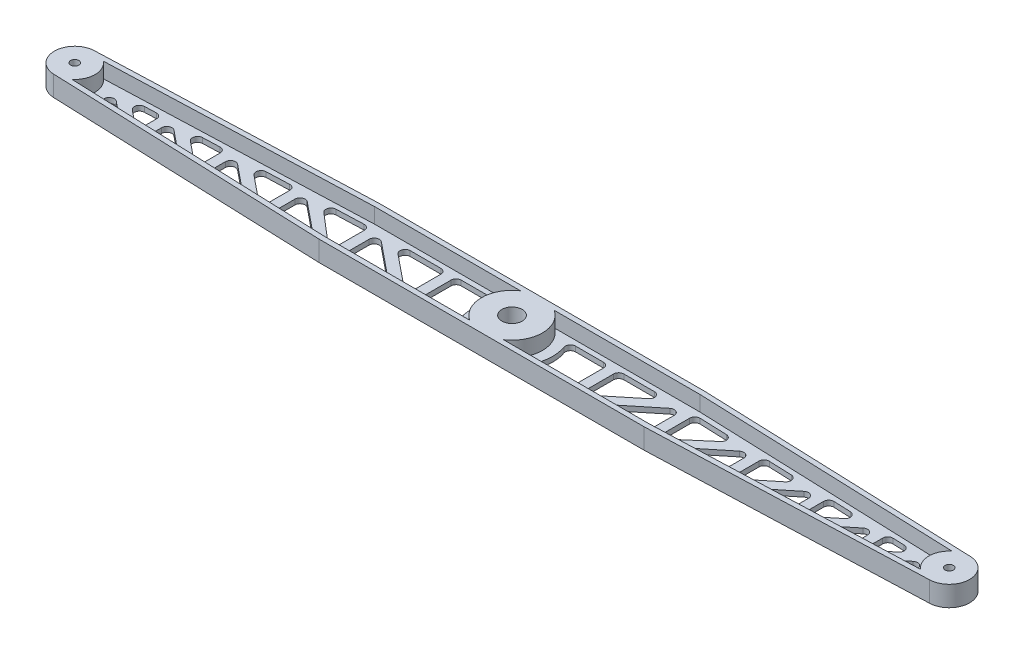
SolidWorks part; units mm, degrees
material "6061 Alloy"
ref_plane "Front Plane" through (0, 0, 0) normal (0, 0, 1) x (1, 0, 0)
ref_plane "Top Plane" through (0, 0, 0) normal (0, 1, 0) x (1, 0, 0)
ref_plane "Right Plane" through (0, 0, 0) normal (1, 0, 0) x (0, 0, -1)
sketch "Sketch1" plane through (0, 0, 0) normal (1, 0, 0) x (0, 0, -1)
  line L1 (-19.05, -6.35) -> (19.05, -6.35)
  line L2 (-19.05, -6.35) -> (-19.05, 6.35)
  line L3 (-19.05, 6.35) -> (19.05, 6.35)
  line L4 (19.05, -6.35) -> (19.05, 6.35)
  line L5 (-19.05, -6.35) -> (19.05, 6.35) construction
  line L6 (-19.05, 6.35) -> (19.05, -6.35) construction
  point P0 (0, 0)
  dimension "D1" = 38.1
  dimension "D2" = 12.7
extrude "Boss-Extrude1" add sketch "Sketch1" along normal mid plane 584.2
sketch "Sketch2" plane through (0, 6.35, 0) normal (0, 1, 0) x (1, 0, 0)
  circle A0 centre (0, 0) radius 6.35
  dimension "D1" = 12.7
extrude "Pivot Hole" cut sketch "Sketch2" against normal through all
hole_wizard "End Holes" positions "Sketch4" profile "Sketch3" tap size "1/4-20" standard "ANSI Inch" end condition through all
sketch "Sketch4" plane through (0, -6.35, 0) normal (0, -1, 0) x (-1, 0, 0)
  line L0 (273.05, 0) -> (292.1, 0) construction
  line L1 (292.1, -19.05) -> (292.1, 19.05) construction
  line L4 (-273.05, 0) -> (-292.1, 0) construction
  line L5 (-292.1, -19.05) -> (-292.1, 19.05) construction
  point P0 (273.05, 0)
  point P2 (-273.05, 0)
  dimension "D1" = 19.05
sketch "Sketch3" plane through (-273.05, -6.35, 0) normal (1, 0, 0) x (0, 0, -1)
  line L0 (0, 0) -> (0, 12.7)
  line L1 (0, 12.7) -> (2.5527, 12.7)
  line L2 (2.5527, 12.7) -> (2.5527, 0)
  line L5 (2.5527, 0) -> (0, 0)
  line L11 (0, -6.35) -> (0, 107.95) construction
  dimension "Thread Major Dia." = 5.1054
  dimension "Thru Tap Drill Depth" = 12.7
sketch "Sketch7" plane through (0, 6.35, 0) normal (0, 1, 0) x (1, 0, 0)
  line L0 (101.6, 19.05) -> (-101.6, 19.05)
  line L1 (292.1, 19.05) -> (-292.1, 19.05) construction
  line L2 (-101.6, 19.05) -> (-273.5194, 12.6913)
  line L3 (-273.5194, -12.6913) -> (-101.6, -19.05)
  line L4 (292.1, -19.05) -> (-292.1, -19.05) construction
  line L5 (-101.6, -19.05) -> (101.6, -19.05)
  line L6 (0, 19.05) -> (0, -19.05) construction
  line L7 (273.5194, -12.6913) -> (101.6, -19.05)
  line L8 (101.6, 19.05) -> (273.5194, 12.6913)
  line L13 (-292.1, 19.05) -> (-292.1, -19.05)
  line L14 (-292.1, -19.05) -> (292.1, -19.05)
  line L15 (292.1, -19.05) -> (292.1, 19.05)
  line L16 (292.1, 19.05) -> (-292.1, 19.05)
  line L17 (-292.1, 19.05) -> (-292.1, -19.05)
  line L18 (-292.1, -19.05) -> (292.1, -19.05)
  line L19 (292.1, -19.05) -> (292.1, 19.05)
  line L20 (292.1, 19.05) -> (-292.1, 19.05)
  arc A0 (-273.5194, 12.6913) -> (-273.5194, -12.6913) centre (-273.05, 0) ccw
  arc A1 (273.5194, 12.6913) -> (273.5194, -12.6913) centre (273.05, 0) cw
  line M4 (-292.1, 19.05) -> (-292.1, -19.05)
  line M5 (-292.1, -19.05) -> (292.1, -19.05)
  line M6 (292.1, -19.05) -> (292.1, 19.05)
  line M7 (292.1, 19.05) -> (-292.1, 19.05)
  dimension "D2" = 12.7
  dimension "D1" = 101.6
  dimension "D3" = 0
extrude "Cut-Extrude3" cut sketch "Sketch7" against normal up to next contours A0 L2 L3 M7 M4 M5 | L8 A1 L7 M5 M6 M7 region at (196.85, 6.35, -17.1073) region at (-187.6315, 6.35, -17.8121)
sketch "Sketch9" plane through (0, 6.35, 0) normal (0, 1, 0) x (1, 0, 0)
  line L0 (-265.0075, 9.829) -> (-101.6, 15.8728)
  line L1 (-101.6, 15.8728) -> (-10.5336, 15.8728)
  line L2 (-10.5336, -15.8728) -> (-101.6, -15.8728)
  line L3 (-101.6, -15.8728) -> (-265.0075, -9.829)
  line L4 (-273.5194, -12.6913) -> (-101.6, -19.05) construction
  line L5 (-101.6, 19.05) -> (-273.5194, 12.6913) construction
  line L6 (0, 0) -> (0, -19.05) construction
  line L7 (101.6, -19.05) -> (-101.6, -19.05) construction
  line L8 (101.6, -15.8728) -> (265.0075, -9.829)
  line L9 (10.5336, -15.8728) -> (101.6, -15.8728)
  line L10 (101.6, 15.8728) -> (10.5336, 15.8728)
  line L11 (265.0075, 9.829) -> (101.6, 15.8728)
  arc A0 (-265.0075, 9.829) -> (-265.0075, -9.829) centre (-273.05, 0) cw
  arc A1 (-273.5194, 12.6913) -> (-273.5194, -12.6913) centre (-273.05, 0) ccw construction
  arc A2 (-10.5336, 15.8728) -> (-10.5336, -15.8728) centre (0, 0) ccw
  arc A3 (10.5336, 15.8728) -> (10.5336, -15.8728) centre (0, 0) cw
  arc A4 (265.0075, 9.829) -> (265.0075, -9.829) centre (273.05, 0) ccw
  dimension "D3" = 19.05
  dimension "D1" = 3.175
  dimension "D2" = 3.175
extrude "Cut-Extrude4" cut sketch "Sketch9" against normal blind 9.525
sketch "Sketch10" plane through (0, -3.175, 0) normal (0, 1, 0) x (1, 0, 0)
  line L0 (-130.0551, 11.6432) -> (-101.6, 12.6957)
  line L1 (-101.6, 12.6957) -> (-101.6, -12.6957)
  line L2 (-101.6, -12.6957) -> (-130.0551, 11.6432)
  line L3 (-140.1121, 11.2712) -> (-111.0553, -12.3459)
  line L4 (-111.0553, -12.3459) -> (-140.1121, -11.2712)
  line L5 (-125.5837, -0.5374) -> (-121.4562, 4.2882) construction
  line L6 (-95.25, 12.6957) -> (-95.25, -12.6957)
  line L7 (-95.25, -12.6957) -> (-64.0104, -12.6957)
  line L8 (-64.0104, -12.6957) -> (-95.25, 12.6957)
  line L9 (-85.1823, 12.6957) -> (-53.9426, -12.6957)
  line L10 (-53.9426, -12.6957) -> (-53.9426, 12.6957)
  line L11 (-53.9426, 12.6957) -> (-85.1823, 12.6957)
  line L12 (-255.3365, 7.0095) -> (-101.6, 12.6957) construction
  line L13 (-101.6, 12.6957) -> (-21.9996, 12.6957) construction
  line L14 (-21.9996, -12.6957) -> (-101.6, -12.6957) construction
  line L15 (-101.6, -12.6957) -> (-255.3365, -7.0095) construction
  line L16 (-265.0075, -9.829) -> (-101.6, -15.8728) construction
  line L17 (-101.6, 15.8728) -> (-265.0075, 9.829) construction
  line L18 (-10.5336, 15.8728) -> (-101.6, 15.8728) construction
  line L19 (-101.6, -15.8728) -> (-10.5336, -15.8728) construction
  line L20 (-255.3365, 7.0095) -> (-237.2662, -7.6779)
  line L21 (-237.2662, -7.6779) -> (-255.3365, -7.0095)
  line L22 (-245.7069, 7.3657) -> (-226.7185, -8.068)
  line L23 (-226.7185, -8.068) -> (-226.7185, 8.068)
  line L24 (-226.7185, 8.068) -> (-245.7069, 7.3657)
  line L25 (-220.3685, 8.3028) -> (-220.3685, -8.3028)
  line L26 (-220.3685, -8.3028) -> (-198.9641, -9.0945)
  line L27 (-198.9641, -9.0945) -> (-220.3685, 8.3028)
  line L28 (-210.739, 8.659) -> (-188.4164, -9.4846)
  line L29 (-188.4164, -9.4846) -> (-188.4164, 9.4846)
  line L30 (-188.4164, 9.4846) -> (-210.739, 8.659)
  line L31 (-182.0664, 9.7195) -> (-182.0664, -9.7195)
  line L32 (-182.0664, -9.7195) -> (-157.0098, -10.6462)
  line L33 (-157.0098, -10.6462) -> (-182.0664, 9.7195)
  line L34 (-246.3013, -0.3342) -> (-242.2962, 4.5934) construction
  line L35 (-209.6663, -0.3958) -> (-205.6612, 4.5318) construction
  line L36 (-172.4369, 10.0757) -> (-146.4621, -11.0364)
  line L37 (-146.4621, -11.0364) -> (-146.4621, 11.0364)
  line L38 (-146.4621, 11.0364) -> (-172.4369, 10.0757)
  line L39 (-140.1121, 11.2712) -> (-140.1121, -11.2712)
  line L40 (-47.5926, 12.6957) -> (-47.5926, -12.6957)
  line L41 (-47.5926, -12.6957) -> (-21.9996, -12.6957)
  line L42 (-169.5381, -0.4634) -> (-165.533, 4.4642) construction
  line L43 (-21.9996, 12.6957) -> (-47.5926, 12.6957)
  line L44 (0, 0) -> (0, 19.05) construction
  line L45 (-79.6302, 0) -> (-75.6251, 4.9276) construction
  line L46 (101.6, 19.05) -> (-101.6, 19.05) construction
  arc A6 (-255.3365, 7.0095) -> (-255.3365, -7.0095) centre (-273.05, 0) cw
  arc A7 (-265.0075, -9.829) -> (-265.0075, 9.829) centre (-273.05, 0) ccw construction
  arc A8 (-21.9996, 12.6957) -> (-21.9996, -12.6957) centre (0, 0) ccw
  arc A9 (-10.5336, 15.8728) -> (-10.5336, -15.8728) centre (0, 0) ccw construction
  dimension "D3" = 6.35
  dimension "D4" = 6.35
  dimension "D1" = 3.175
  dimension "D2" = 3.175
  dimension "D5" = 6.35
  dimension "D6" = 6.35
  dimension "D7" = 6.35
  dimension "D8" = 6.35
  dimension "D9" = 6.35
  dimension "D10" = 6.35
extrude "Cut-Extrude5" cut sketch "Sketch10" against normal up to next
fillet "Fillet3" radius 3.175 34 edges at (-21.9996, -4.7625, 12.6957) (-21.9996, -4.7625, -12.6957) (-47.5926, -4.7625, -12.6957) (-47.5926, -4.7625, 12.6957) (-53.9426, -4.7625, 12.6957) (-53.9426, -4.7625, -12.6957) (-85.1823, -4.7625, -12.6957) (-64.0104, -4.7625, 12.6957) (-95.25, -4.7625, -12.6957) (-95.25, -4.7625, 12.6957) (-101.6, -4.7625, 12.6957) (-130.0551, -4.7625, -11.6432) (-101.6, -4.7625, -12.6957) (-111.0553, -4.7625, 12.3459) (-140.1121, -4.7625, -11.2712) (-140.1121, -4.7625, 11.2712) (-146.4621, -4.7625, 11.0364) (-146.4621, -4.7625, -11.0364) (-172.4369, -4.7625, -10.0757) (-157.0098, -4.7625, 10.6462) (-182.0664, -4.7625, -9.7195) (-182.0664, -4.7625, 9.7195) (-188.4164, -4.7625, 9.4846) (-188.4164, -4.7625, -9.4846) (-210.739, -4.7625, -8.659) (-198.9641, -4.7625, 9.0945) (-220.3685, -4.7625, -8.3028) (-220.3685, -4.7625, 8.3028) (-226.7185, -4.7625, 8.068) (-226.7185, -4.7625, -8.068) (-245.7069, -4.7625, -7.3657) (-237.2662, -4.7625, 7.6779) (-255.3365, -4.7625, 7.0095) (-255.3365, -4.7625, -7.0095)
mirror "Mirror1" about plane through (0, 0, 0) normal (1, 0, 0) of "Fillet3", "Cut-Extrude5"
